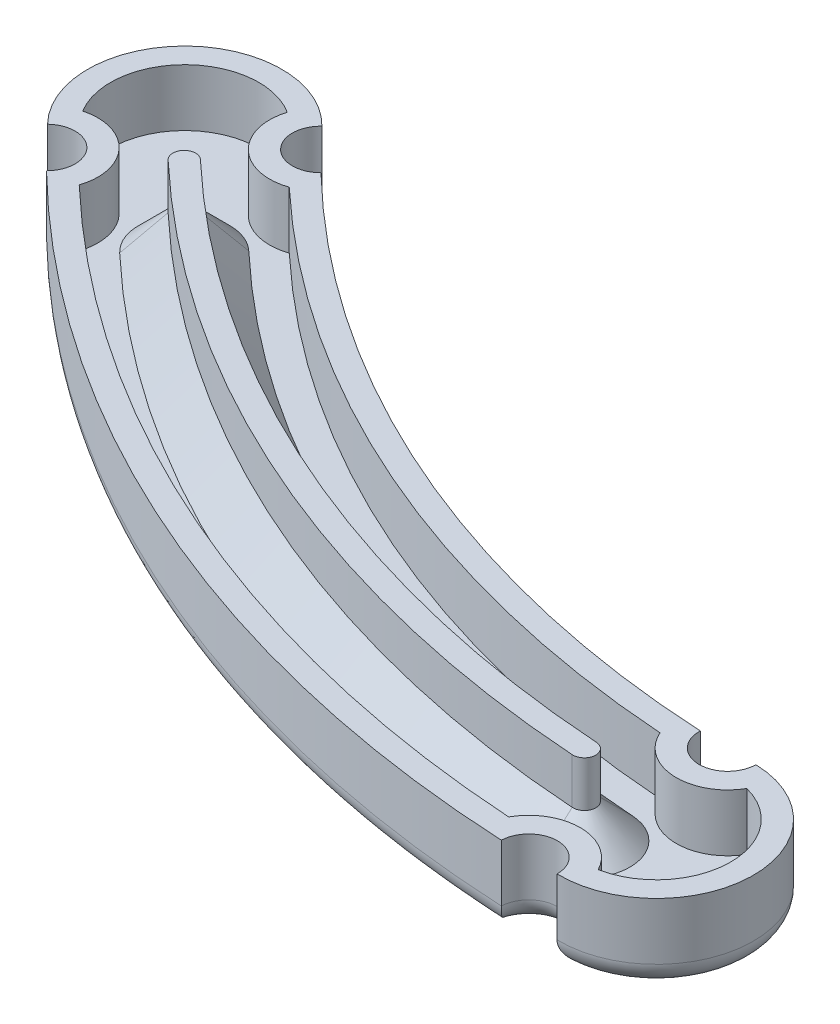
SolidWorks part; units mm, degrees
ref_plane "Front Plane" through (0, 0, 0) normal (0, 0, 1) x (1, 0, 0)
ref_plane "Top Plane" through (0, 0, 0) normal (0, 1, 0) x (1, 0, 0)
ref_plane "Right Plane" through (0, 0, 0) normal (1, 0, 0) x (0, 0, -1)
sketch "Sketch2" plane through (0, 0, 0) normal (0, 1, 0) x (1, 0, 0)
  line L0 (-71.3503, -82.2054) -> (-34958.9124, 35734.8019) construction
  line L1 (-70.1201, -59.1107) -> (-34995.8073, 35720.7213) construction
  line L2 (-39.7979, -107.5277) -> (49945.2079, -1331.9458) construction
  line L3 (31.7139, -92.3079) -> (50015.3873, -1369.9589) construction
  circle A0 centre (0, 0) radius 100 construction
  arc A1 (-0.2082, -108.4975) -> (0.2172, -91.5028) centre (0, -100) ccw
  arc A2 (-67.2386, -62.0626) -> (-79.4101, -73.9309) centre (-73.3212, -68) ccw
  arc A3 (-63.7464, -65.6403) -> (-4.7807, -91.375) centre (0, 0) ccw
  arc A4 (-75.9216, -77.5123) -> (-5.2063, -108.375) centre (0, 0) ccw
  arc A5 (-67.2386, -62.0626) -> (-63.7464, -65.6403) centre (-65.5159, -63.8743) ccw
  arc A6 (-75.9216, -77.5123) -> (-79.4101, -73.9309) centre (-77.6873, -75.7425) ccw
  arc A7 (-4.7807, -91.375) -> (0.2172, -91.5028) centre (-2.2826, -91.4715) ccw
  arc A8 (-0.2082, -108.4975) -> (-5.2063, -108.375) centre (-2.708, -108.4662) ccw
  dimension "D1" = 200
  dimension "D3" = 17
  dimension "D4" = 5
  dimension "D2" = 80
extrude "Boss-Extrude1" add sketch "Sketch2" along normal blind 7
fillet "Fillet1" radius 2 8 edges at (8.4973, 0, 100.2127) (-2.3465, 0, 93.9707) (-36.6, 0, 83.8611) (-67.3049, 0, 65.6206) (-79.2553, 0, 61.9143) (-75.8965, 0, 73.9981) (-43.4, 0, 99.4419) (-2.6467, 0, 105.967)
shell "Shell1" thickness 2 removed face at (-37.3691, 7, 85.6233)
sketch "Sketch3" plane through (0, 2, 0) normal (0, 1, 0) x (1, 0, 0)
  line L0 (-73.4141, -77.1532) -> (-64.0404, -68.1255) construction
  line L1 (-6.403, -93.2805) -> (-6.648, -106.2923) construction
  arc A0 (-68.7273, -72.6393) -> (-6.5255, -99.7864) centre (0, 0) ccw construction
  arc A1 (-73.4141, -77.1532) -> (-6.648, -106.2923) centre (0, 0) ccw construction
  arc A2 (1.2759, -106.3736) -> (-6.648, -106.2923) centre (-2.708, -108.4662) ccw construction
  arc A3 (-69.4145, -73.3657) -> (-6.5908, -100.7843) centre (0, 0) ccw
  arc A4 (-68.04, -71.9129) -> (-6.4603, -98.7885) centre (0, 0) ccw
  arc A5 (-69.4145, -73.3657) -> (-68.04, -71.9129) centre (-68.7273, -72.6393) cw
  arc A6 (-6.5908, -100.7843) -> (-6.4603, -98.7885) centre (-6.5255, -99.7864) ccw
  point P16 (-6.5255, -99.7864)
  dimension "D1" = 1
  dimension "D2" = 1
extrude "Boss-Extrude2" add sketch "Sketch3" along normal offset from surface (7 mm away) 2 up to face at (-37.4529, 7, 85.8155) offset beyond the face yes
chamfer "Chamfer2" distance 3 angle 45 4 edges at (-39.5998, 2, 90.7346) (-69.4536, 2, 71.9521) (-5.5276, 2, 99.8517) (-40.3998, 2, 92.5676)
